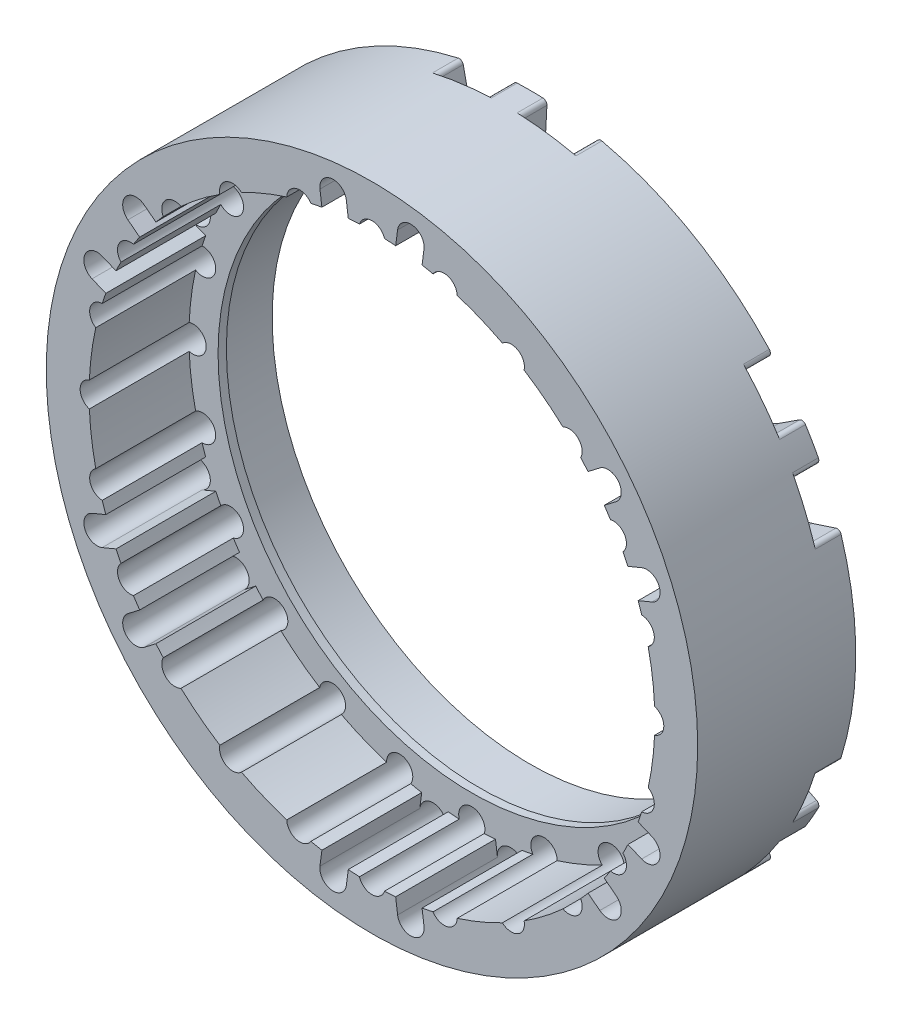
SolidWorks part; units mm, degrees
material "ABS"
ref_plane "Front Plane" through (0, 0, 0) normal (0, 0, 1) x (1, 0, 0)
ref_plane "Top Plane" through (0, 0, 0) normal (0, 1, 0) x (1, 0, 0)
ref_plane "Right Plane" through (0, 0, 0) normal (1, 0, 0) x (0, 0, -1)
sketch "CYC Master Sketch" plane through (0, 0, 0) normal (0, 0, 1) x (1, 0, 0)
  circle A0 centre (0, 0) radius 39.15
  circle A2 centre (0, 0) radius 33.5 construction
  circle A3 centre (-33.5, 0) radius 1.575
  circle A4 centre (-32.3585, 8.6704) radius 1.575
  circle A5 centre (-29.0119, 16.75) radius 1.575
  circle A6 centre (-23.6881, 23.6881) radius 1.575
  circle A7 centre (-16.75, 29.0119) radius 1.575
  circle A8 centre (-8.6704, 32.3585) radius 1.575
  circle A9 centre (0, 33.5) radius 1.575
  circle A10 centre (8.6704, 32.3585) radius 1.575
  circle A11 centre (16.75, 29.0119) radius 1.575
  circle A12 centre (23.6881, 23.6881) radius 1.575
  circle A13 centre (29.0119, 16.75) radius 1.575
  circle A14 centre (32.3585, 8.6704) radius 1.575
  circle A15 centre (33.5, 0) radius 1.575
  circle A16 centre (32.3585, -8.6704) radius 1.575
  circle A17 centre (29.0119, -16.75) radius 1.575
  circle A18 centre (23.6881, -23.6881) radius 1.575
  circle A19 centre (16.75, -29.0119) radius 1.575
  circle A20 centre (8.6704, -32.3585) radius 1.575
  circle A21 centre (0, -33.5) radius 1.575
  circle A22 centre (-8.6704, -32.3585) radius 1.575
  circle A23 centre (0, 0) radius 34
  circle A24 centre (-16.75, -29.0119) radius 1.575
  circle A25 centre (-23.6881, -23.6881) radius 1.575
  circle A26 centre (-29.0119, -16.75) radius 1.575
  circle A27 centre (-32.3585, -8.6704) radius 1.575
  circle A28 centre (0, 0) radius 31 construction
  circle A29 centre (0, 0) radius 24.975 construction
  circle A30 centre (0, 0) radius 35.75 construction
  circle A31 centre (4.6663, -35.4442) radius 1.6
  circle A32 centre (-4.6663, -35.4442) radius 1.6
  circle A33 centre (-28.3624, -21.7632) radius 1.6
  circle A34 centre (-33.0287, -13.6809) radius 1.6
  circle A35 centre (-33.0287, 13.6809) radius 1.6
  circle A36 centre (-28.3624, 21.7632) radius 1.6
  circle A37 centre (-4.6663, 35.4442) radius 1.6
  circle A38 centre (4.6663, 35.4442) radius 1.6
  circle A39 centre (28.3624, 21.7632) radius 1.6
  circle A40 centre (33.0287, 13.6809) radius 1.6
  circle A41 centre (33.0287, -13.6809) radius 1.6
  circle A42 centre (28.3624, -21.7632) radius 1.6
  point P47 (0, 0)
  point P72 (0, 0)
  point P82 (0, 0)
extrude "Gearbox Wall" add sketch "CYC Master Sketch" along normal blind 19 contours A0 A23 A13 A14 A15 A16 A17 A18 A19 A20 A21 A22 A3 A4 A5 A6 A7 A8 A9 A10 A11 A12 region at (-38.0427, 0, 0)
extrude "Gearbox Bottom" add sketch "CYC Master Sketch<3>" along normal blind 7 contours A21 A23 | A23 A20 | A20 A23 | A23 A19 | A19 A23 | A23 A18 | A18 A23 | A23 A17 | A17 A23 | A23 A16 | A16 A23 | A23 A15 | A15 A23 | A23 A14 | A14 A23 | A23 A13 | A13 A23 | A23 A12 | A12 A23 | A23 A11 | A11 A23 | A23 A10 | A10 A23 | A23 A9 | A9 A23 | A23 A8 | A8 A23 | A23 A7 | A7 A23 | A23 A6 | A6 A23 | A23 A5 | A5 A23 | A23 A4 | A4 A23 | A23 A3 | A3 A23 | A23 A22 | A22 A23 | A13 A23 A12 A11 A10 A9 A8 A7 A6 A5 A4 A3 A22 A21 A20 A19 A18 A17 A16 A15 A14 | A24 | A25 | A26 | A27 | A21 region at (-33.0866, 0, 0) region at (0, 0, 0) region at (-34.4394, 0, 0) region at (-31.9592, 8.5634, 0) region at (-33.2659, 8.9136, 0) region at (-28.6538, 16.5433, 0) region at (-29.8254, 17.2197, 0) region at (-23.3958, 23.3958, 0) region at (-24.3523, 24.3523, 0) region at (-16.5433, 28.6538, 0) region at (-17.2197, 29.8254, 0) region at (-8.5634, 31.9592, 0) region at (-8.9136, 33.2659, 0) region at (-8.9136, -33.2659, 0) region at (-8.5634, -31.9592, 0) region at (0, 33.0866, 0) region at (0, 34.4394, 0) region at (0, -33.0866, 0) region at (8.5634, 31.9592, 0) region at (8.9136, 33.2659, 0) region at (8.9136, -33.2659, 0) region at (8.5634, -31.9592, 0) region at (16.5433, 28.6538, 0) region at (17.2197, 29.8254, 0) region at (17.2197, -29.8254, 0) region at (16.5433, -28.6538, 0) region at (23.3958, 23.3958, 0) region at (24.3523, 24.3523, 0) region at (24.3523, -24.3523, 0) region at (23.3958, -23.3958, 0) region at (28.6538, 16.5433, 0) region at (29.8254, 17.2197, 0) region at (29.8254, -17.2197, 0) region at (28.6538, -16.5433, 0) region at (31.9592, 8.5634, 0) region at (33.2659, 8.9136, 0) region at (33.2659, -8.9136, 0) region at (31.9592, -8.5634, 0) region at (33.0866, 0, 0) region at (34.4394, 0, 0)
sketch "CYC Master Sketch<3>" plane through (0, 0, 0) normal (0, 0, 1) x (1, 0, 0) same geometry as "CYC Master Sketch"
extrude "Pin Cut" cut sketch "CYC Master Sketch<2>" against normal blind 4 from surface contours A23 A7 | A7 A23 | A23 A6 | A6 A23 | A23 A5 | A5 A23 | A23 A4 | A4 A23 | A23 A3 | A3 A23 | A23 A22 | A22 A23 | A23 A21 | A21 A23 | A23 A20 | A20 A23 | A23 A19 | A19 A23 | A23 A18 | A18 A23 | A23 A17 | A17 A23 | A16 A23 | A23 A16 | A15 A23 | A23 A15 | A23 A14 | A14 A23 | A23 A13 | A13 A23 | A23 A12 | A12 A23 | A23 A11 | A11 A23 | A10 A23 | A23 A9 | A9 A23 | A23 A8 | A8 A23 | A23 A10 | A23 A24 | A23 A24 | A23 A25 | A23 A25 | A23 A26 | A23 A26 | A23 A27 | A23 A27 region at (-33.0866, 0, 0) region at (-34.4394, 0, 0) region at (-31.9592, 8.5634, 0) region at (-33.2659, 8.9136, 0) region at (-31.9592, -8.5634, 0) region at (-33.2659, -8.9136, 0) region at (-28.6538, 16.5433, 0) region at (-29.8254, 17.2197, 0) region at (-28.6538, -16.5433, 0) region at (-29.8254, -17.2197, 0) region at (-23.3958, 23.3958, 0) region at (-24.3523, 24.3523, 0) region at (-23.3958, -23.3958, 0) region at (-24.3523, -24.3523, 0) region at (-16.5433, 28.6538, 0) region at (-17.2197, 29.8254, 0) region at (-16.5433, -28.6538, 0) region at (-17.2197, -29.8254, 0) region at (-8.5634, 31.9592, 0) region at (-8.9136, 33.2659, 0) region at (-8.9136, -33.2659, 0) region at (-8.5634, -31.9592, 0) region at (0, 33.0866, 0) region at (0, 34.4394, 0) region at (0, -34.4394, 0) region at (0, -33.0866, 0) region at (8.5634, 31.9592, 0) region at (8.9136, 33.2659, 0) region at (8.9136, -33.2659, 0) region at (8.5634, -31.9592, 0) region at (16.5433, 28.6538, 0) region at (17.2197, 29.8254, 0) region at (17.2197, -29.8254, 0) region at (16.5433, -28.6538, 0) region at (23.3958, 23.3958, 0) region at (24.3523, 24.3523, 0) region at (24.3523, -24.3523, 0) region at (23.3958, -23.3958, 0) region at (28.6538, 16.5433, 0) region at (29.8254, 17.2197, 0) region at (29.8254, -17.2197, 0) region at (28.6538, -16.5433, 0) region at (31.9592, 8.5634, 0) region at (33.2659, 8.9136, 0) region at (33.2659, -8.9136, 0) region at (31.9592, -8.5634, 0) region at (33.0866, 0, 0) region at (34.4394, 0, 0) starting at face at (0, 0, 7)
sketch "CYC Master Sketch<2>" plane through (0, 0, 0) normal (0, 0, 1) x (1, 0, 0) same geometry as "CYC Master Sketch"
sketch "CYC Master" plane through (0, 0, 7) normal (0, 0, 1) x (1, 0, 0)
  circle A0 centre (0, 0) radius 39.15
  circle A2 centre (0, 0) radius 33.5 construction
  circle A3 centre (-33.5, 0) radius 1.575
  circle A4 centre (-32.3585, 8.6704) radius 1.575
  circle A5 centre (-29.0119, 16.75) radius 1.575
  circle A6 centre (-23.6881, 23.6881) radius 1.575
  circle A7 centre (-16.75, 29.0119) radius 1.575
  circle A8 centre (-8.6704, 32.3585) radius 1.575
  circle A9 centre (0, 33.5) radius 1.575
  circle A10 centre (8.6704, 32.3585) radius 1.575
  circle A11 centre (16.75, 29.0119) radius 1.575
  circle A12 centre (23.6881, 23.6881) radius 1.575
  circle A13 centre (29.0119, 16.75) radius 1.575
  circle A14 centre (32.3585, 8.6704) radius 1.575
  circle A15 centre (33.5, 0) radius 1.575
  circle A16 centre (32.3585, -8.6704) radius 1.575
  circle A17 centre (29.0119, -16.75) radius 1.575
  circle A18 centre (23.6881, -23.6881) radius 1.575
  circle A19 centre (16.75, -29.0119) radius 1.575
  circle A20 centre (8.6704, -32.3585) radius 1.575
  circle A21 centre (0, -33.5) radius 1.575
  circle A22 centre (-8.6704, -32.3585) radius 1.575
  circle A23 centre (0, 0) radius 34
  circle A24 centre (-16.75, -29.0119) radius 1.575
  circle A25 centre (-23.6881, -23.6881) radius 1.575
  circle A26 centre (-29.0119, -16.75) radius 1.575
  circle A27 centre (-32.3585, -8.6704) radius 1.575
  circle A28 centre (0, 0) radius 31 construction
  circle A29 centre (0, 0) radius 24.975 construction
  circle A30 centre (0, 0) radius 35.75 construction
  circle A31 centre (4.6663, -35.4442) radius 1.6
  circle A32 centre (-4.6663, -35.4442) radius 1.6
  circle A33 centre (-28.3624, -21.7632) radius 1.6
  circle A34 centre (-33.0287, -13.6809) radius 1.6
  circle A35 centre (-33.0287, 13.6809) radius 1.6
  circle A36 centre (-28.3624, 21.7632) radius 1.6
  circle A37 centre (-4.6663, 35.4442) radius 1.6
  circle A38 centre (4.6663, 35.4442) radius 1.6
  circle A39 centre (28.3624, 21.7632) radius 1.6
  circle A40 centre (33.0287, 13.6809) radius 1.6
  circle A41 centre (33.0287, -13.6809) radius 1.6
  circle A42 centre (28.3624, -21.7632) radius 1.6
  point P47 (0, 0)
  point P72 (0, 0)
  point P82 (0, 0)
sketch "Sketch2" plane through (0, 0, 7) normal (0, 0, 1) x (1, 0, 0)
  circle A0 centre (0, 0) radius 31
  circle A1 centre (0, 0) radius 31 construction
extrude "Housing Bearing Cut" cut sketch "Sketch2" against normal through all
sketch "Sketch3" plane through (0, 0, 7) normal (0, 0, 1) x (1, 0, 0)
  circle A0 centre (0, 0) radius 31
  circle A1 centre (0, 0) radius 30.5
  circle A2 centre (0, 0) radius 31 construction
  dimension "D1" = 61
  dimension "Housing Bearing Outer (Driven)" = 62
extrude "Housing Bearing Retainer" add sketch "Sketch3" against normal blind 0.5
sketch "Sketch5" plane through (0, 0, 0) normal (0, 0, -1) x (-1, 0, 0)
  line L0 (0, 0) -> (31.7579, 16.1759) construction
  line L1 (0, 0) -> (33.8943, 11.0181) construction
  line L2 (33.8943, 11.0181) -> (37.2322, 12.1031)
  line L3 (31.7579, 16.1759) -> (34.8854, 17.7689)
  line L4 (0, 0) -> (33.9049, 19.575) construction
  line L5 (26.4891, 23.8443) -> (29.0977, 26.1925)
  line L6 (29.8877, 19.4152) -> (32.831, 21.3271)
  line L7 (33.8943, -11.0181) -> (37.2322, -12.1031)
  line L8 (31.7579, -16.1759) -> (34.8854, -17.7689)
  line L9 (26.4891, -23.8443) -> (29.0977, -26.1925)
  line L10 (29.8877, -19.4152) -> (32.831, -21.3271)
  line L11 (7.4052, -34.8624) -> (8.1345, -38.2956)
  line L12 (1.8702, -35.5911) -> (2.0543, -39.0961)
  line L13 (-7.4052, -34.8624) -> (-8.1345, -38.2956)
  line L14 (-1.8702, -35.5911) -> (-2.0543, -39.0961)
  line L15 (-26.4891, -23.8443) -> (-29.0977, -26.1925)
  line L16 (-29.8877, -19.4152) -> (-32.831, -21.3271)
  line L17 (-33.8943, -11.0181) -> (-37.2322, -12.1031)
  line L18 (-31.7579, -16.1759) -> (-34.8854, -17.7689)
  line L19 (-33.8943, 11.0181) -> (-37.2322, 12.1031)
  line L20 (-31.7579, 16.1759) -> (-34.8854, 17.7689)
  line L21 (-26.4891, 23.8443) -> (-29.0977, 26.1925)
  line L22 (-29.8877, 19.4152) -> (-32.831, 21.3271)
  line L23 (-7.4052, 34.8624) -> (-8.1345, 38.2956)
  line L24 (-1.8702, 35.5911) -> (-2.0543, 39.0961)
  line L25 (7.4052, 34.8624) -> (8.1345, 38.2956)
  line L26 (1.8702, 35.5911) -> (2.0543, 39.0961)
  arc A0 (31.7579, 16.1759) -> (33.8943, 11.0181) centre (33.0287, 13.6809) ccw
  arc A1 (-32.831, -21.3271) -> (-29.0977, -26.1925) centre (0, 0) ccw
  circle A2 centre (0, 0) radius 39.15 construction
  arc A3 (34.8854, 17.7689) -> (37.2322, 12.1031) centre (0, 0) cw
  arc A4 (32.831, 21.3271) -> (29.0977, 26.1925) centre (0, 0) ccw
  arc A5 (29.8877, 19.4152) -> (26.4891, 23.8443) centre (28.3624, 21.7632) cw
  arc A6 (34.8854, -17.7689) -> (37.2322, -12.1031) centre (0, 0) ccw
  arc A7 (31.7579, -16.1759) -> (33.8943, -11.0181) centre (33.0287, -13.6809) cw
  arc A8 (32.831, -21.3271) -> (29.0977, -26.1925) centre (0, 0) cw
  arc A9 (29.8877, -19.4152) -> (26.4891, -23.8443) centre (28.3624, -21.7632) ccw
  arc A10 (2.0543, -39.0961) -> (8.1345, -38.2956) centre (0, 0) ccw
  arc A11 (1.8702, -35.5911) -> (7.4052, -34.8624) centre (4.6663, -35.4442) cw
  arc A12 (-2.0543, -39.0961) -> (-8.1345, -38.2956) centre (0, 0) cw
  arc A13 (-1.8702, -35.5911) -> (-7.4052, -34.8624) centre (-4.6663, -35.4442) ccw
  arc A14 (-29.8877, -19.4152) -> (-26.4891, -23.8443) centre (-28.3624, -21.7632) cw
  arc A15 (-34.8854, -17.7689) -> (-37.2322, -12.1031) centre (0, 0) cw
  arc A16 (-31.7579, -16.1759) -> (-33.8943, -11.0181) centre (-33.0287, -13.6809) ccw
  arc A17 (-34.8854, 17.7689) -> (-37.2322, 12.1031) centre (0, 0) ccw
  arc A18 (-31.7579, 16.1759) -> (-33.8943, 11.0181) centre (-33.0287, 13.6809) cw
  arc A19 (-32.831, 21.3271) -> (-29.0977, 26.1925) centre (0, 0) cw
  arc A20 (-29.8877, 19.4152) -> (-26.4891, 23.8443) centre (-28.3624, 21.7632) ccw
  arc A21 (-2.0543, 39.0961) -> (-8.1345, 38.2956) centre (0, 0) ccw
  arc A22 (-1.8702, 35.5911) -> (-7.4052, 34.8624) centre (-4.6663, 35.4442) cw
  arc A23 (2.0543, 39.0961) -> (8.1345, 38.2956) centre (0, 0) cw
  arc A24 (1.8702, 35.5911) -> (7.4052, 34.8624) centre (4.6663, 35.4442) ccw
  point P39 (0, 0)
  dimension "D1" = 5.6
  dimension "D3" = 6
  dimension "D2" = 7.5
extrude "M3 Socket Head Cutout" cut sketch "Sketch5" against normal blind 3.1
fillet "Fillet1" radius 0.5 24 edges at (-8.1345, -38.2956, 1.55) (-2.0543, -39.0961, 1.55) (2.0543, -39.0961, 1.55) (8.1345, -38.2956, 1.55) (-29.0977, -26.1925, 1.55) (-32.831, -21.3271, 1.55) (-37.2322, -12.1031, 1.55) (-34.8854, -17.7689, 1.55) (-29.0977, 26.1925, 1.55) (-32.831, 21.3271, 1.55) (-34.8854, 17.7689, 1.55) (-37.2322, 12.1031, 1.55) (-8.1345, 38.2956, 1.55) (-2.0543, 39.0961, 1.55) (8.1345, 38.2956, 1.55) (2.0543, 39.0961, 1.55) (29.0977, 26.1925, 1.55) (32.831, 21.3271, 1.55) (34.8854, 17.7689, 1.55) (37.2322, 12.1031, 1.55) (37.2322, -12.1031, 1.55) (34.8854, -17.7689, 1.55) (32.831, -21.3271, 1.55) (29.0977, -26.1925, 1.55)
sketch "Sketch6" plane through (0, 0, 19) normal (0, 0, 1) x (1, 0, 0)
  line L0 (-6.0193, 33.4629) -> (-6.2526, 35.2353)
  line L1 (-2.8467, 33.8806) -> (-3.08, 35.653)
  line L2 (0, 0) -> (-4.6663, 35.4442) construction
  line L3 (-6.0193, 33.4629) -> (-2.8467, 33.8806)
  line L4 (2.8467, 33.8806) -> (3.08, 35.653)
  line L5 (6.0193, 33.4629) -> (6.2526, 35.2353)
  line L6 (2.8467, 33.8806) -> (6.0193, 33.4629)
  line L7 (0, 0) -> (4.6663, 35.4442) construction
  line L8 (0, 0) -> (-2.8467, 33.8806) construction
  line L9 (0, 0) -> (6.0193, 33.4629) construction
  arc A0 (-1.5043, 33.9667) -> (-7.3382, 33.1987) centre (0, 0) ccw construction
  circle A1 centre (-4.6663, 35.4442) radius 1.6 construction
  arc A2 (-3.08, 35.653) -> (-6.2526, 35.2353) centre (-4.6663, 35.4442) ccw
  arc A3 (6.2526, 35.2353) -> (3.08, 35.653) centre (4.6663, 35.4442) ccw
  dimension "D1" = 2
  dimension "D2" = 15
  dimension "D3" = 34
extrude "Cut-Extrude1" cut sketch "Sketch6" against normal up to surface (12 mm away) contours A2 L0 L3 L1 | L4 A3 L5 L6 up to face at (0, 0, 7)
pattern_circular "CirPattern1" count 6 over 360 about axis through (0, 0, 0) along (0, 0, 1) of "Cut-Extrude1", "Housing Bearing Cut"
sketch "Sketch7" plane through (0, 0, 7) normal (0, 0, 1) x (1, 0, 0)
  circle A0 centre (0, 0) radius 31
  circle A1 centre (0, 0) radius 31 construction
  circle A2 centre (0, 0) radius 30.5
  dimension "D1" = 61
extrude "Boss-Extrude1" add sketch "Sketch7" against normal blind 1
